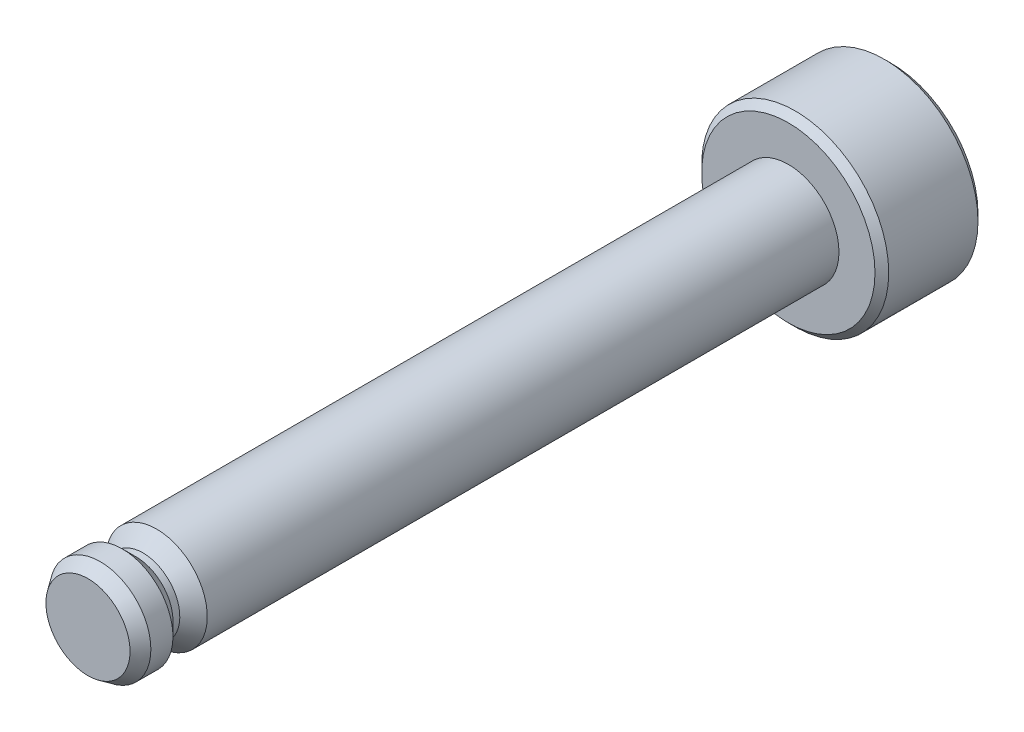
SolidWorks part; units mm, degrees
ref_plane "Front" through (0, 0, 0) normal (0, 0, 1) x (1, 0, 0)
ref_plane "Top" through (0, 0, 0) normal (0, 1, 0) x (1, 0, 0)
ref_plane "Right" through (0, 0, 0) normal (1, 0, 0) x (0, 0, -1)
sketch "Sketch2" plane through (0, 0, 0) normal (0, 0, 1) x (1, 0, 0)
  circle A0 centre (0, 0) radius 1.475
  dimension "D1" = 2.95
extrude "Shaft" add sketch "Sketch2" along normal blind 20.4
sketch "Sketch5" plane through (0, 0, 0) normal (0, 0, 1) x (1, 0, 0)
  circle A0 centre (0, 0) radius 2.725
  dimension "D1" = 5.45
extrude "Head" add sketch "Sketch5" against normal blind 3
chamfer "Chamfer1" distance 0.25 angle 55 1 edges at (1.475, 0, 20.4) first distance on face at (1.475, 0, 20.4)
chamfer "Deburs" distance 0.2 angle 45 2 edges at (2.725, 0, 0) (2.725, 0, -3)
sketch "Sketch6" plane through (0, 0, 0) normal (1, 0, 0) x (0, 0, -1)
  line L0 (0, 0) -> (-18.9, 0) construction
  line L1 (-18.9, 0) -> (-18.9, 1.075) construction
  line L2 (0, 1.475) -> (-20.043, 1.475) construction
  line L3 (-19.4, 1.475) -> (-18.4, 1.475)
  line L4 (-18.4, 1.475) -> (-18.8, 1.075)
  line L5 (-18.8, 1.075) -> (-19, 1.075)
  line L6 (-19, 1.075) -> (-19.4, 1.475)
  line L7 (-18.9, 1.075) -> (-18.9, 1.475) construction
  dimension "D2" = 0.4
  dimension "D3" = 1
revolve "e-Clip Notch Long" cut sketch "Sketch6" angle 360 about L0
equation "\"D1@Sketch2\"=\"Plastic Hardware OD@Box Assy.Assembly\""
equation "\"D1@Sketch5\"=\"Hardware Head Countersink Diameter@Box Assy.Assembly\"-.3mm"
equation "\"D1@Head\"=\"Countersink Depth@Box Assy.Assembly\""
equation "\"Length\" = 20mm"
equation "\"D1@Shaft\"=\"Length\"+.4mm"
equation "\"D1@Sketch6\"=\"Length\"-1.1mm"
